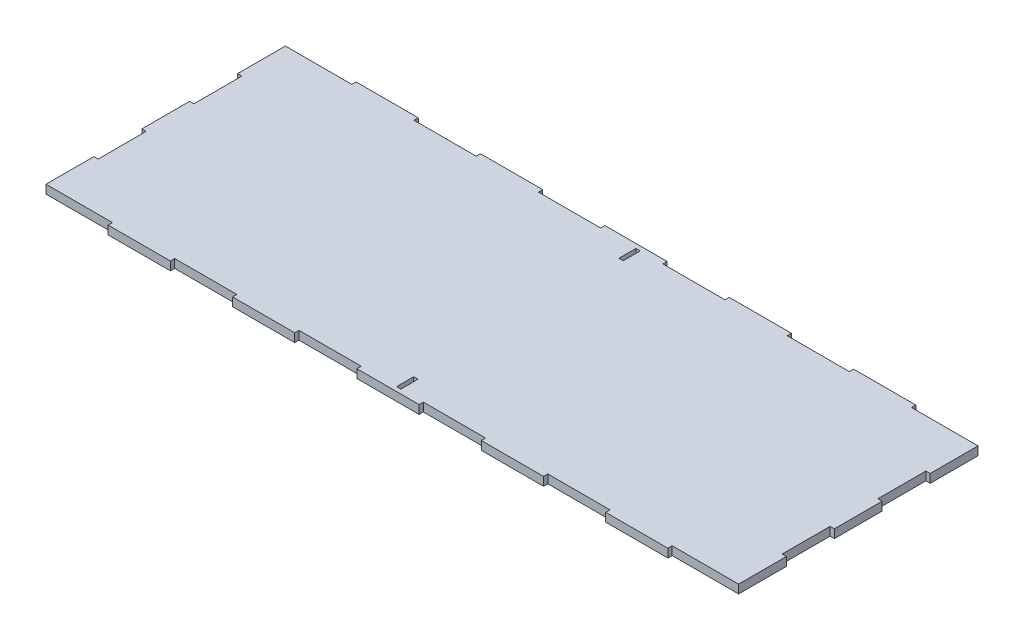
SolidWorks part; units mm, degrees
ref_plane "Front Plane" through (0, 0, 0) normal (0, 0, 1) x (1, 0, 0)
ref_plane "Top Plane" through (0, 0, 0) normal (0, 1, 0) x (1, 0, 0)
ref_plane "Right Plane" through (0, 0, 0) normal (1, 0, 0) x (0, 0, -1)
sketch "Sketch1" plane through (0, 0, 0) normal (0, 1, 0) x (1, 0, 0)
  line L0 (0, 0) -> (508, 0)
  line L1 (508, 0) -> (508, 177.8)
  line L2 (508, 177.8) -> (0, 177.8)
  line L3 (0, 177.8) -> (0, 0)
  line L4 (0, 0) -> (0, -3.175)
  line L5 (0, -3.175) -> (46.1818, -3.175)
  line L6 (46.1818, -3.175) -> (46.1818, 0)
  line L7 (46.1818, 0) -> (0, 0)
  line L8 (46.1818, 0) -> (46.1818, -3.175)
  line L9 (46.1818, -3.175) -> (92.3636, -3.175)
  line L10 (92.3636, -3.175) -> (92.3636, 0)
  line L11 (92.3636, 0) -> (46.1818, 0)
  line L12 (92.3636, 0) -> (92.3636, -3.175)
  line L13 (92.3636, -3.175) -> (138.5455, -3.175)
  line L14 (138.5455, -3.175) -> (138.5455, 0)
  line L15 (138.5455, 0) -> (92.3636, 0)
  line L16 (138.5455, 0) -> (138.5455, -3.175)
  line L17 (138.5455, -3.175) -> (184.7273, -3.175)
  line L18 (184.7273, -3.175) -> (184.7273, 0)
  line L19 (184.7273, 0) -> (138.5455, 0)
  line L20 (184.7273, 0) -> (184.7273, -3.175)
  line L21 (184.7273, -3.175) -> (230.9091, -3.175)
  line L22 (230.9091, -3.175) -> (230.9091, 0)
  line L23 (230.9091, 0) -> (184.7273, 0)
  line L24 (230.9091, 0) -> (230.9091, -3.175)
  line L25 (230.9091, -3.175) -> (277.0909, -3.175)
  line L26 (277.0909, -3.175) -> (277.0909, 0)
  line L27 (277.0909, 0) -> (230.9091, 0)
  line L28 (277.0909, 0) -> (277.0909, -3.175)
  line L29 (277.0909, -3.175) -> (323.2727, -3.175)
  line L30 (323.2727, -3.175) -> (323.2727, 0)
  line L31 (323.2727, 0) -> (277.0909, 0)
  line L32 (323.2727, 0) -> (323.2727, -3.175)
  line L33 (323.2727, -3.175) -> (369.4545, -3.175)
  line L34 (369.4545, -3.175) -> (369.4545, 0)
  line L35 (369.4545, 0) -> (323.2727, 0)
  line L36 (369.4545, 0) -> (369.4545, -3.175)
  line L37 (369.4545, -3.175) -> (415.6364, -3.175)
  line L38 (415.6364, -3.175) -> (415.6364, 0)
  line L39 (415.6364, 0) -> (369.4545, 0)
  line L40 (415.6364, 0) -> (415.6364, -3.175)
  line L41 (415.6364, -3.175) -> (461.8182, -3.175)
  line L42 (461.8182, -3.175) -> (461.8182, 0)
  line L43 (461.8182, 0) -> (415.6364, 0)
  line L44 (461.8182, 0) -> (461.8182, -3.175)
  line L45 (461.8182, -3.175) -> (508, -3.175)
  line L46 (508, -3.175) -> (508, 0)
  line L47 (508, 0) -> (461.8182, 0)
  line L48 (0, 0) -> (46.1818, 0) construction
  line L49 (0, 177.8) -> (-3.175, 177.8)
  line L50 (-3.175, 177.8) -> (-3.175, 142.24)
  line L51 (-3.175, 142.24) -> (0, 142.24)
  line L52 (0, 142.24) -> (0, 177.8)
  line L53 (0, 142.24) -> (-3.175, 142.24)
  line L54 (-3.175, 142.24) -> (-3.175, 106.68)
  line L55 (-3.175, 106.68) -> (0, 106.68)
  line L56 (0, 106.68) -> (0, 142.24)
  line L57 (0, 106.68) -> (-3.175, 106.68)
  line L58 (-3.175, 106.68) -> (-3.175, 71.12)
  line L59 (-3.175, 71.12) -> (0, 71.12)
  line L60 (0, 71.12) -> (0, 106.68)
  line L61 (0, 71.12) -> (-3.175, 71.12)
  line L62 (-3.175, 71.12) -> (-3.175, 35.56)
  line L63 (-3.175, 35.56) -> (0, 35.56)
  line L64 (0, 35.56) -> (0, 71.12)
  line L65 (0, 35.56) -> (-3.175, 35.56)
  line L66 (-3.175, 35.56) -> (-3.175, 0)
  line L67 (-3.175, 0) -> (0, 0)
  line L68 (0, 0) -> (0, 35.56)
  line L69 (0, 177.8) -> (0, 142.24) construction
  line L70 (0, 88.9) -> (508, 88.9) construction
  line L71 (254, 177.8) -> (254, 0) construction
  line L72 (461.8182, 177.8) -> (415.6364, 177.8)
  line L73 (461.8182, 180.975) -> (461.8182, 177.8)
  line L74 (415.6364, 180.975) -> (461.8182, 180.975)
  line L75 (415.6364, 177.8) -> (415.6364, 180.975)
  line L76 (369.4545, 177.8) -> (323.2727, 177.8)
  line L77 (369.4545, 180.975) -> (369.4545, 177.8)
  line L78 (323.2727, 180.975) -> (369.4545, 180.975)
  line L79 (323.2727, 177.8) -> (323.2727, 180.975)
  line L80 (277.0909, 177.8) -> (230.9091, 177.8)
  line L81 (277.0909, 180.975) -> (277.0909, 177.8)
  line L82 (230.9091, 180.975) -> (277.0909, 180.975)
  line L83 (230.9091, 177.8) -> (230.9091, 180.975)
  line L84 (184.7273, 177.8) -> (138.5455, 177.8)
  line L85 (184.7273, 180.975) -> (184.7273, 177.8)
  line L86 (138.5455, 180.975) -> (184.7273, 180.975)
  line L87 (138.5455, 177.8) -> (138.5455, 180.975)
  line L88 (92.3636, 177.8) -> (46.1818, 177.8)
  line L89 (92.3636, 180.975) -> (92.3636, 177.8)
  line L90 (46.1818, 180.975) -> (92.3636, 180.975)
  line L91 (46.1818, 177.8) -> (46.1818, 180.975)
  line L92 (508, 0) -> (508, 35.56)
  line L93 (511.175, 0) -> (508, 0)
  line L94 (511.175, 35.56) -> (511.175, 0)
  line L95 (508, 35.56) -> (511.175, 35.56)
  line L96 (508, 71.12) -> (508, 106.68)
  line L97 (511.175, 71.12) -> (508, 71.12)
  line L98 (511.175, 106.68) -> (511.175, 71.12)
  line L99 (508, 106.68) -> (511.175, 106.68)
  line L100 (508, 142.24) -> (508, 177.8)
  line L101 (511.175, 142.24) -> (508, 142.24)
  line L102 (511.175, 177.8) -> (511.175, 142.24)
  line L103 (508, 177.8) -> (511.175, 177.8)
  dimension "D1" = 508
  dimension "D2" = 177.8
  dimension "D3" = 3.175
  dimension "D4" = 46.1818
  dimension "D6" = 46.1818
  dimension "D7" = 3.175
  dimension "D9" = 35.56
  dimension "D10" = 35.56
  dimension "D5" = 11
  dimension "D8" = 5
extrude "Boss-Extrude1" add sketch "Sketch1" along normal blind 6.35 contours L2 L3 L0 L1 | L75 L2 L73 L74 | L79 L2 L77 L78 | L83 L2 L81 L82 | L87 L2 L85 L86 | L91 L2 L89 L90 | L50 L51 L3 L49 | L58 L59 L3 L55 | L66 L67 L3 L63 | L33 L34 L0 L30 | L41 L42 L0 L38 | L95 L1 L93 L94 | L99 L1 L97 L98 | L103 L1 L101 L102 | L9 L10 L11 L8 | L17 L18 L19 L16 | L25 L26 L27 L24 region at (254, 0, -88.9) region at (-1.5875, 0, -17.78) region at (-1.5875, 0, -88.9) region at (-1.5875, 0, -160.02) region at (69.2727, 0, -179.3875) region at (346.3636, 0, 1.5875) region at (161.6364, 0, -179.3875) region at (438.7273, 0, 1.5875) region at (254, 0, -179.3875) region at (509.5875, 0, -17.78) region at (346.3636, 0, -179.3875) region at (509.5875, 0, -88.9) region at (438.7273, 0, -179.3875) region at (509.5875, 0, -160.02)
sketch "Sketch2" plane through (0, 6.35, 0) normal (0, 1, 0) x (1, 0, 0)
  line L0 (254, 180.975) -> (254, -3.175) construction
  line L1 (230.9091, 180.975) -> (277.0909, 180.975) construction
  line L2 (230.9091, -3.175) -> (277.0909, -3.175) construction
  line L3 (277.0909, 0) -> (323.2727, 0) construction
  line L4 (260.35, 0) -> (260.35, 12.7)
  line L5 (260.35, 12.7) -> (257.175, 12.7)
  line L6 (257.175, 12.7) -> (257.175, 0)
  line L7 (257.175, 0) -> (260.35, 0)
  line L8 (-3.175, 88.9) -> (511.175, 88.9) construction
  line L9 (-3.175, 106.68) -> (-3.175, 71.12) construction
  line L10 (511.175, 106.68) -> (511.175, 71.12) construction
  line L11 (257.175, 165.1) -> (257.175, 177.8)
  line L12 (260.35, 165.1) -> (257.175, 165.1)
  line L13 (260.35, 177.8) -> (260.35, 165.1)
  line L14 (257.175, 177.8) -> (260.35, 177.8)
  dimension "D1" = 12.7
  dimension "D2" = 3.175
  dimension "D3" = 3.175
extrude "Cut-Extrude1" cut sketch "Sketch2" against normal up to surface (6.35 mm away) up to face at (254, 0, -88.9)
equation "\"Height\"= 12in"
equation "\"Depth\"= 7in"
equation "\"WallThickness\"= 0.125in"
equation "\"FloorThickness\"= 0.25in"
equation "\"Width\" = 30in"
equation "\"D7@Sketch1\"=\"WallThickness\""
equation "\"D1@Boss-Extrude1\"=\"FloorThickness\""
equation "\"D2@Sketch2\"=\"WallThickness\""
equation "\"D3@Sketch2\"=\"FloorThickness\"/2"
